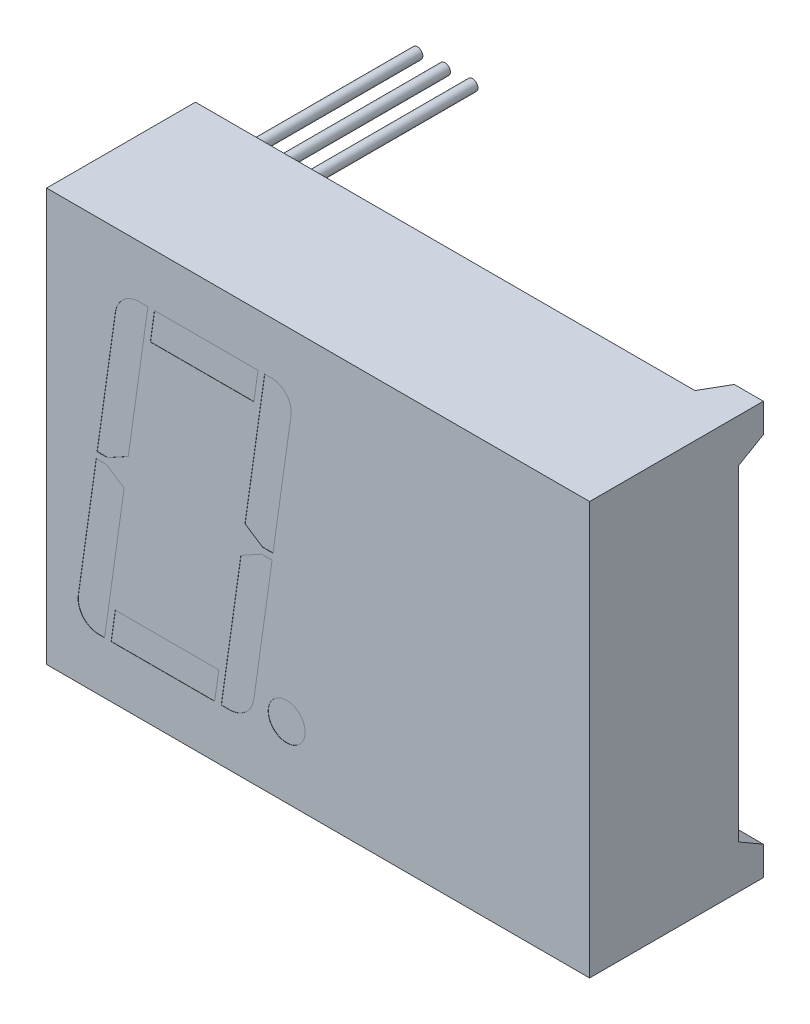
SolidWorks part; units mm, degrees
ref_plane "Plan de face" through (0, 0, 0) normal (0, 0, 1) x (1, 0, 0)
ref_plane "Plan de dessus" through (0, 0, 0) normal (0, 1, 0) x (1, 0, 0)
ref_plane "Plan de droite" through (0, 0, 0) normal (1, 0, 0) x (0, 0, -1)
sketch "Sketch1" plane through (0, 0, 0) normal (0, 0, 1) x (1, 0, 0)
  line L1 (12.5, -9.5) -> (-12.5, -9.5)
  line L2 (12.5, -9.5) -> (12.5, 9.5)
  line L3 (12.5, 9.5) -> (-12.5, 9.5)
  line L4 (-12.5, -9.5) -> (-12.5, 9.5)
  line L5 (12.5, -9.5) -> (-12.5, 9.5) construction
  line L6 (12.5, 9.5) -> (-12.5, -9.5) construction
  point P0 (0, 0)
  dimension "D1" = 25
  dimension "D2" = 19
extrude "Boss-Extrude1" add sketch "Sketch1" along normal blind 8
sketch "Sketch8" plane through (12.5, 0, 0) normal (1, 0, 0) x (0, 0, -1)
  line L0 (0, 0) -> (-8, 0) construction
  line L1 (0, -9.5) -> (0, 9.5) construction
  line L2 (-8, -9.5) -> (-8, 9.5) construction
  line L3 (-1.15, 7.5) -> (-1.15, -7.5)
  line L4 (-1.15, -7.5) -> (0, -8.164)
  line L5 (0, 8.164) -> (0, -8.164)
  line L6 (-8, -9.5) -> (0, -9.5) construction
  line L7 (-1.15, 7.5) -> (0, 8.164)
  point P13 (-1.15, 0)
  dimension "D1" = 1.15
  dimension "D2" = 2
  dimension "D3" = 120
extrude "Cut-Extrude9" cut sketch "Sketch8" against normal up to next
sketch "Sketch6" plane through (0, -9.5, 0) normal (0, -1, 0) x (1, 0, 0)
  line L0 (11.164, 0) -> (10.5, 1.15)
  line L3 (-12.5, 0) -> (12.5, 0) construction
  line L4 (10.5, 1.15) -> (-12.5, 1.15)
  line L7 (-12.5, 8) -> (-12.5, 0) construction
  line L8 (-12.5, 1.15) -> (-12.5, 0)
  line L9 (-12.5, 0) -> (11.164, 0)
  line L10 (12.5, 8) -> (12.5, 0) construction
  dimension "D1" = 2
  dimension "D2" = 120
  dimension "D3" = 1.15
extrude "Cut-Extrude3" cut sketch "Sketch6" against normal up to surface (19 mm away) up to face at (0, 9.5, 4)
sketch "Sketch7" plane through (0, 0, 1.15) normal (0, 0, -1) x (-1, 0, 0)
  line L1 (12.5, 0) -> (-12.5, 0) construction
  line L6 (-12.5, 7.5) -> (-12.5, -7.5) construction
  line L8 (12.5, -9.5) -> (12.5, 9.5) construction
  circle A0 centre (9.96, 7.62) radius 0.25
  circle A1 centre (8.69, 7.62) radius 0.25
  circle A2 centre (11.23, 7.62) radius 0.25
  circle A3 centre (9.96, -7.65) radius 0.25
  circle A4 centre (8.69, -7.65) radius 0.25
  circle A5 centre (11.23, -7.65) radius 0.25
  dimension "D3" = 3
  dimension "D2" = 0.5
  dimension "D1" = 1.27
  dimension "D6" = 7.62
  dimension "D4" = 2
extrude "Boss-Extrude2" add sketch "Sketch7" along normal blind 8.95
sketch "Sketch9" plane through (0, 0, 8) normal (0, 0, 1) x (1, 0, 0)
  line L0 (-12.5, 0) -> (12.5, 0) construction
  line L1 (-12.5, 9.5) -> (-12.5, -9.5) construction
  line L2 (12.5, -9.5) -> (12.5, 9.5) construction
  line L3 (-6.15, 9.5) -> (-6.15, -9.5) construction
  line L4 (12.5, 9.5) -> (-12.5, 9.5) construction
  line L5 (-12.5, -9.5) -> (12.5, -9.5) construction
  line L6 (-9.2022, 7.1) -> (-11.1978, -7.1) construction
  line L7 (-11.1978, -7.1) -> (-3.0978, -7.1) construction
  line L8 (-3.0978, -7.1) -> (-1.1022, 7.1) construction
  line L9 (-1.1022, 7.1) -> (-9.2022, 7.1) construction
  line L10 (-5.1522, 7.1) -> (-7.1478, -7.1) construction
  line L11 (-3.5826, -7.1) -> (-1.5869, 7.1) construction
  line L12 (-1.2919, 5.75) -> (-9.3919, 5.75) construction
  line L13 (-10.7131, -7.1) -> (-8.7174, 7.1) construction
  line L14 (-9.8346, -7.1) -> (-7.8389, 7.1) construction
  line L15 (-4.4611, -7.1) -> (-2.4654, 7.1) construction
  line L16 (-2.9081, -5.75) -> (-11.0081, -5.75) construction
  line L17 (-2.0789, 0.15) -> (-10.1789, 0.15) construction
  line L18 (-2.1211, -0.15) -> (-10.2211, -0.15) construction
  line L19 (-10.1789, 0.15) -> (-9.3389, 6.1268)
  line L20 (-8.2194, 7.1) -> (-7.8389, 7.1)
  line L21 (-7.8389, 7.1) -> (-8.7419, 0.675)
  line L22 (-8.7419, 0.675) -> (-9.6942, 0.15)
  line L23 (-9.6942, 0.15) -> (-10.1789, 0.15)
  line L24 (-2.0789, 0.15) -> (-2.5636, 0.15)
  line L25 (-2.5636, 0.15) -> (-3.3684, 0.675)
  line L26 (-3.3684, 0.675) -> (-2.4654, 7.1)
  line L27 (-2.4654, 7.1) -> (-2.1419, 7.1)
  line L28 (-1.2469, 6.0704) -> (-2.0789, 0.15)
  line L29 (-2.0051, 0.675) -> (-10.1051, 0.675) construction
  line L30 (-2.1949, -0.675) -> (-10.2949, -0.675) construction
  line L31 (-10.2211, -0.15) -> (-9.7364, -0.15)
  line L32 (-9.7364, -0.15) -> (-8.9316, -0.675)
  line L33 (-8.9316, -0.675) -> (-9.8346, -7.1)
  line L34 (-9.8346, -7.1) -> (-10.1004, -7.1)
  line L35 (-11.0451, -6.0132) -> (-10.2211, -0.15)
  line L36 (-2.1211, -0.15) -> (-2.9581, -6.1055)
  line L37 (-4.1022, -7.1) -> (-4.4611, -7.1)
  line L38 (-4.4611, -7.1) -> (-3.5587, -0.6788)
  line L39 (-3.5587, -0.6788) -> (-2.6058, -0.15)
  line L40 (-2.6058, -0.15) -> (-2.1211, -0.15)
  line L41 (-9.3419, -5.75) -> (-4.5743, -5.75)
  line L42 (-4.5743, -5.75) -> (-4.7641, -7.1)
  line L43 (-4.7641, -7.1) -> (-9.5316, -7.1)
  line L44 (-9.5316, -7.1) -> (-9.3419, -5.75)
  line L45 (-7.5359, 7.1) -> (-2.7684, 7.1)
  line L46 (-2.7684, 7.1) -> (-2.9581, 5.75)
  line L47 (-2.9581, 5.75) -> (-7.7257, 5.75)
  line L48 (-7.7257, 5.75) -> (-7.5359, 7.1)
  circle A0 centre (-1.45, -6.25) radius 0.85
  arc A1 (-9.3389, 6.1268) -> (-8.2194, 7.1) centre (-8.2194, 5.9695) cw
  arc A2 (-2.1419, 7.1) -> (-1.2469, 6.0704) centre (-2.1419, 6.1962) cw
  arc A3 (-10.1004, -7.1) -> (-11.0451, -6.0132) centre (-10.1004, -6.146) cw
  arc A4 (-2.9581, -6.1055) -> (-4.1022, -7.1) centre (-4.1022, -5.9447) cw
  point P6 (-6.15, 0)
  point P15 (-10.2, 0)
  point P21 (-6.15, 0)
  point P26 (-2.5847, 0)
  point P31 (-9.7153, 0)
  point P32 (-5.3419, 5.75)
  point P35 (-8.8367, 0)
  point P38 (-3.4633, 0)
  point P41 (-6.9581, -5.75)
  point P44 (-6.1289, 0.15)
  point P47 (-6.1711, -0.15)
  point P60 (-6.0551, 0.675)
  point P63 (-6.2449, -0.675)
  dimension "D4" = 1.7
  dimension "D1" = 6.35
  dimension "D2" = 8.1
  dimension "D3" = 14.2
  dimension "D5" = 4.7
  dimension "D6" = 0.48
  dimension "D7" = 1.35
  dimension "D8" = 0.48
  dimension "D9" = 1.35
  dimension "D10" = 1.35
  dimension "D11" = 1.35
  dimension "D12" = 0.15
  dimension "D13" = 0.15
  dimension "D14" = 0.675
  dimension "D15" = 0.675
  dimension "D16" = 0.3
  dimension "D17" = 0.3
  dimension "D18" = 0.3
  dimension "D19" = 0.3
  dimension "D20" = 8
extrude "Cut-Extrude10" cut sketch "Sketch9" against normal blind 0.01
